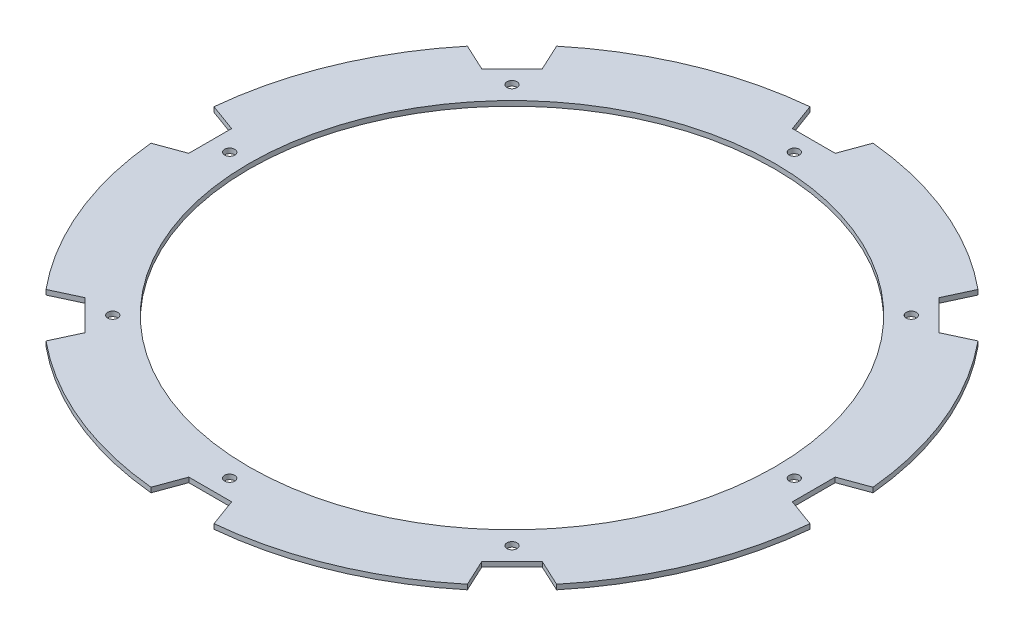
SolidWorks part; units mm, degrees
ref_plane "Front Plane" through (0, 0, 0) normal (0, 0, 1) x (1, 0, 0)
ref_plane "Top Plane" through (0, 0, 0) normal (0, 1, 0) x (1, 0, 0)
ref_plane "Right Plane" through (0, 0, 0) normal (1, 0, 0) x (0, 0, -1)
sketch "Sketch2" plane through (0, 0, 0) normal (0, 1, 0) x (1, 0, 0)
  line L0 (-215.9, 0) -> (-171.45, 0) construction
  line L1 (-171.45, 0) -> (0, 0) construction
  line L2 (0, 0) -> (171.45, 0) construction
  line L3 (171.45, 0) -> (215.9, 0) construction
  line L4 (-214.9183, 20.5652) -> (-196.85, 13.97)
  line L5 (-196.85, 13.97) -> (-196.85, -13.97)
  line L6 (-196.85, -13.97) -> (-214.9175, -20.574)
  circle A0 centre (0, 0) radius 171.45
  circle A1 centre (0, 0) radius 215.9
  circle A2 centre (-184.15, 0) radius 3.302
  point P10 (-196.85, 0)
  point P13 (-196.85, 0)
  point P15 (-171.45, 0)
  dimension "D1" = 342.9
  dimension "D2" = 431.8
  dimension "D7" = 6.604
  dimension "D3" = 27.94
  dimension "D4" = 6.5952
  dimension "D5" = 6.604
  dimension "D6" = 25.4
  dimension "D8" = 12.7
extrude "Boss-Extrude1" add sketch "Sketch2" along normal blind 3.175 contours L6 A1 L4 L5 A2 A0 region at (10.0035, 0, -209.5617)
pattern_circular "CirPattern1" count 8 over 360 about axis through (0, 3.175, 0) along (0, -1, 0) reverse direction yes of face at (-184.15, 3.175, 3.302) of face at (-196.85, 1.5875, 0) of face at (-205.8837, 1.5875, 17.272) of face at (-205.8842, 1.5875, -17.2676)
sketch "Sketch3" plane through (0, 3.175, 0) normal (0, 1, 0) x (1, 0, 0)
  line L0 (-196.85, 13.97) -> (-196.85, -13.97) construction
  line L1 (0, 0) -> (-171.45, 0) construction
  line L2 (-171.45, 0) -> (-196.85, 0) construction
  line L3 (-196.85, 0) -> (-228.5886, 0) construction
  circle A0 centre (0, 0) radius 171.45 construction
  point P0 (-196.85, 0)
  point P1 (0, 0)
  point P4 (-171.45, 0)
